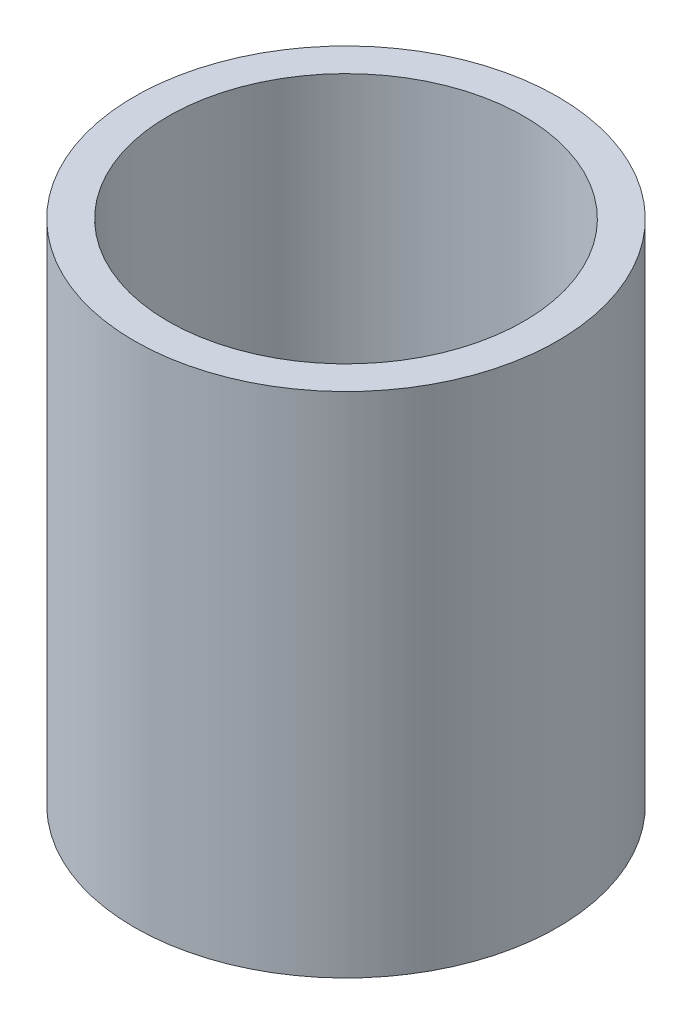
SolidWorks part; units mm, degrees
ref_plane "Front Plane" through (0, 0, 0) normal (0, 0, 1) x (1, 0, 0)
ref_plane "Top Plane" through (0, 0, 0) normal (0, 1, 0) x (1, 0, 0)
ref_plane "Right Plane" through (0, 0, 0) normal (1, 0, 0) x (0, 0, -1)
sketch "Sketch1" plane through (0, 0, 0) normal (0, 1, 0) x (1, 0, 0)
  circle A0 centre (0, 0) radius 12.5
  circle A1 centre (0, 0) radius 10.5
  dimension "D1" = 2
extrude "Boss-Extrude1" add sketch "Sketch1" along normal blind 30
sketch "Sketch2" plane through (0, 0, 0) normal (0, 0, 1) x (1, 0, 0)
  line L1 (10.5, 30) -> (20.5, 30)
  line L2 (10.5, 30) -> (10.5, 0)
  line L3 (10.5, 0) -> (20.5, 0)
  line L4 (20.5, 30) -> (20.5, 0)
  dimension "D1" = 10
ref_axis "pivot" through (0, 30, 0) along (0, -1, 0)
ref_plane "midplane" through (0, 15, 0) normal (0, 1, 0) x (1, 0, 0)
